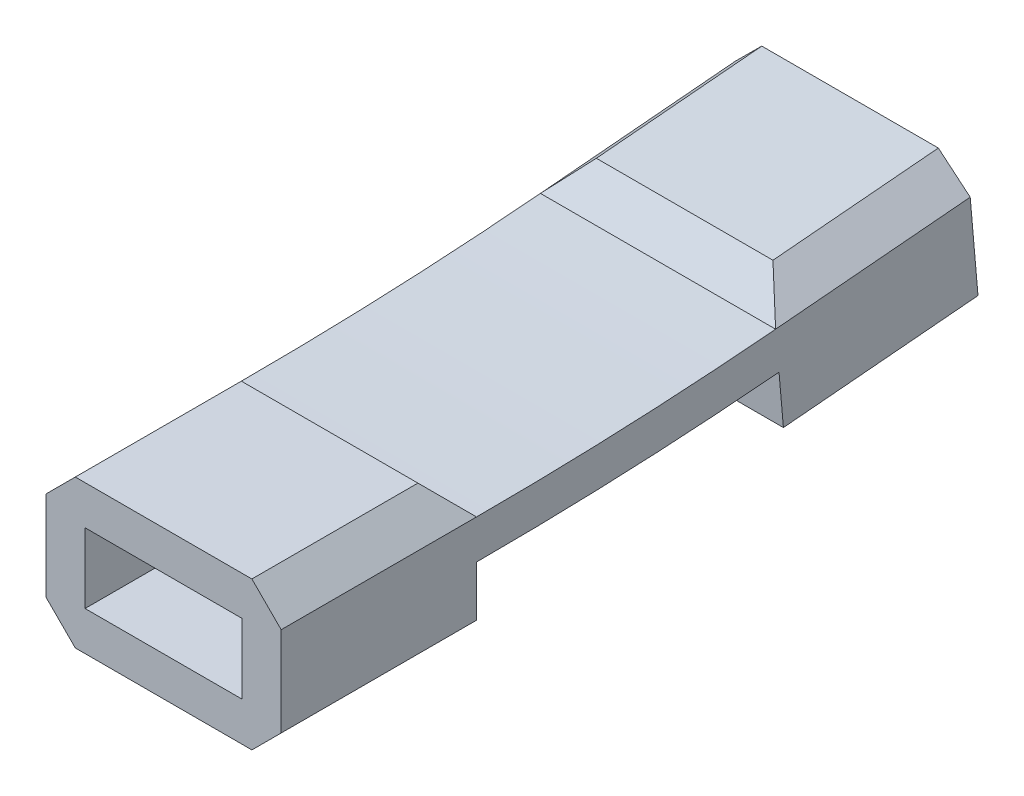
SolidWorks part; units mm, degrees
note: The reader was unsure of these and kept them because the rebuilt part matched: shared geometry of "Sketch1<2>", "Sketch5<4>".
ref_plane "Front Plane" through (0, 0, 0) normal (0, 0, 1) x (1, 0, 0)
ref_plane "Top Plane" through (0, 0, 0) normal (0, 1, 0) x (1, 0, 0)
ref_plane "Right Plane" through (0, 0, 0) normal (1, 0, 0) x (0, 0, -1)
other "Configuration Table"
sketch "Sketch1" plane through (0, 0, 0) normal (0, 0, 1) x (1, 0, 0)
  line L1 (4.02, -1.79) -> (-4.02, -1.79)
  line L2 (4.02, -1.79) -> (4.02, 1.79)
  line L3 (4.02, 1.79) -> (-4.02, 1.79)
  line L4 (-4.02, -1.79) -> (-4.02, 1.79)
  line L5 (0, 1.79) -> (0, -1.79) construction
  line L6 (4.02, 0) -> (-4.02, 0) construction
  line L7 (-6.02, 3.79) -> (6.02, 3.79)
  line L8 (-6.02, 3.79) -> (-6.02, -3.79)
  line L9 (-6.02, -3.79) -> (6.02, -3.79)
  line L10 (6.02, 3.79) -> (6.02, -3.79)
  line L11 (0, -3.79) -> (0, 3.79) construction
  line L12 (-6.02, 0) -> (6.02, 0) construction
  point P0 (0, 0)
  point P4 (0, 0)
  dimension "D1" = 3.58
  dimension "D2" = 8.04
  dimension "D3" = 2
  dimension "D4" = 2
extrude "Boss-Extrude1" add sketch "Sketch1" along normal blind 8
extrude "Boss-Extrude2" add sketch "Sketch1<2>" against normal blind 2 contours L4 L1 L2 L3 | L10 L7 L8 L9 L1 L4 L3 L2
sketch "Sketch1<2>" plane through (0, 0, 0) normal (0, 0, 1) x (1, 0, 0) same geometry as "Sketch1"
sketch "Sketch3" plane through (6.02, 9.81, 0) normal (1, 0, 0) x (0, -1, 0)
  line L0 (13.6, 2) -> (9.52, 2)
  line L2 (8.8439, 17.4852) -> (12.9084, 17.8408)
  line L3 (13.6, -8) -> (13.6, 2) construction
  arc A1 (9.52, 2) -> (8.8439, 17.4852) centre (-168.153, 2) ccw
  arc A3 (12.9084, 17.8408) -> (13.6, 2) centre (-168.153, 2) cw construction
  dimension "D1" = 4.08
  dimension "D4" = 5
  dimension "D2" = 15.5
extrude "Extrude-Thin1" add sketch "Sketch3" along normal up to surface (12.04 mm away) thin contours L0 A1 L2
sketch "Sketch5" plane through (0, -2.2254, -17.7645) normal (0, 0.0872, -0.9962) x (-1, 0, 0)
  line L1 (4.02, 1.1237) -> (-4.02, 1.1237)
  line L2 (4.02, 1.1237) -> (4.02, 4.7037)
  line L3 (4.02, 4.7037) -> (-4.02, 4.7037)
  line L4 (-4.02, 1.1237) -> (-4.02, 4.7037)
  line L5 (0, 4.7037) -> (0, 1.1237) construction
  line L6 (4.02, 2.9137) -> (-4.02, 2.9137) construction
  line L7 (-6.02, 6.7037) -> (6.02, 6.7037)
  line L8 (-6.02, 6.7037) -> (-6.02, -0.8763)
  line L9 (-6.02, -0.8763) -> (6.02, -0.8763)
  line L10 (6.02, 6.7037) -> (6.02, -0.8763)
  line L11 (0, -0.8763) -> (0, 6.7037) construction
  line L12 (-6.02, 2.9137) -> (6.02, 2.9137) construction
  line L13 (6.02, -0.8763) -> (-6.02, -0.8763) construction
  point P0 (0, 2.9137)
  point P4 (0, 2.9137)
  dimension "D1" = 3.58
  dimension "D2" = 8.04
  dimension "D3" = 2
  dimension "D4" = 2
extrude "Boss-Extrude4" add sketch "Sketch5" along normal blind 10
extrude "Boss-Extrude5" add sketch "Sketch5<4>" along normal blind 2 contours L8 L7 L10 L9
sketch "Sketch5<4>" plane through (0, -2.2254, -17.7645) normal (0, 0.0872, -0.9962) x (-1, 0, 0) same geometry as "Sketch5"
chamfer "Chamfer1" distance 1.5 angle 45 12 edges at (6.02, -2.6626, -22.8218) (-6.02, -2.6626, -22.8218) (-6.02, 4.8886, -22.1612) (6.02, 4.8886, -22.1612) (6.02, 3.79, 3) (6.02, -3.79, 3) (-6.02, -3.79, 3) (-6.02, 3.79, 3) (0, 3.79, -2) (0, -3.0984, -17.8408) (0, -3.79, -2) (0, 4.4528, -17.1802)
equation "\"LF\" = 0.04mm"
equation "\"TF\" = 0.02mm"
equation "\"AngLF\"= 0.5"
equation "\"AngTF\"= 0.3"
equation "\"D2@Sketch1\"=8+2*\"TF\""
equation "\"D1@Sketch1\"=3.5+2*\"LF\""
